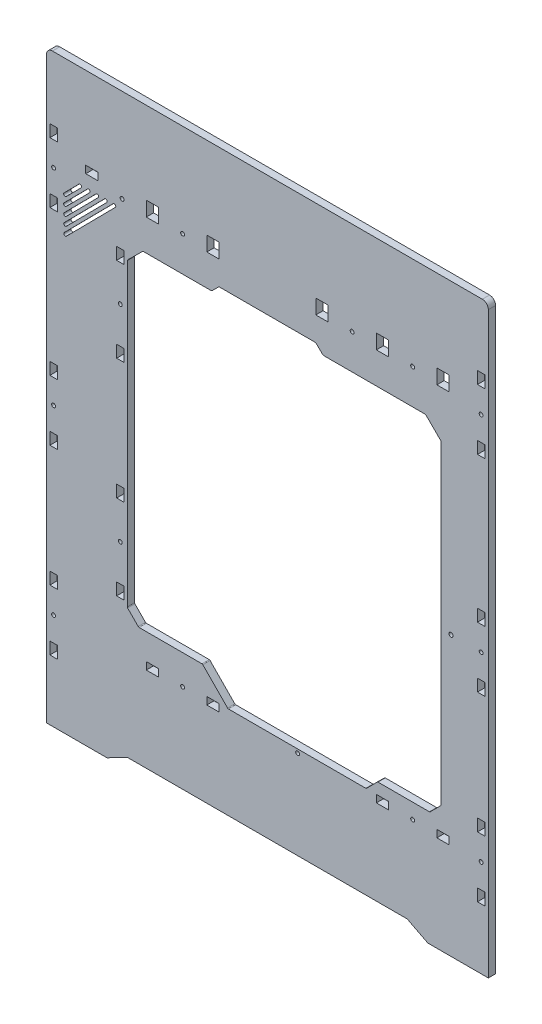
SolidWorks part; units mm, degrees
material "Клен"
ref_plane "Front" through (0, 0, 0) normal (0, 0, 1) x (1, 0, 0)
ref_plane "Top" through (0, 0, 0) normal (0, 1, 0) x (1, 0, 0)
ref_plane "Right" through (0, 0, 0) normal (1, 0, 0) x (0, 0, -1)
sketch "Эскиз1" plane through (0, 0, 0) normal (0, 0, 1) x (1, 0, 0)
  line L1 (768.3665, 485.0072) -> (768.3665, 477.0072)
  line L2 (745.3154, 525.0072) -> (1160.2565, 525.0072) construction
  line L3 (768.3665, 485.0072) -> (768.3665, 520.0072)
  line L4 (773.3665, 525.0072) -> (1128.3665, 525.0072)
  line L5 (1133.3665, 520.0072) -> (1133.3665, 485.0072)
  line L8 (1124.3665, 292.0072) -> (1130.4665, 292.0072)
  line L9 (1124.3665, 302.0072) -> (1124.3665, 292.0072)
  line L10 (1130.4665, 302.0072) -> (1124.3665, 302.0072)
  line L11 (1130.4665, 292.0072) -> (1130.4665, 302.0072)
  line L32 (1133.3665, 42.0072) -> (1133.3665, 477.0072)
  line L42 (768.3665, 477.0072) -> (768.3665, 42.0072)
  line L43 (768.3665, 42.0072) -> (818.3665, 42.0072)
  line L44 (818.3665, 42.0072) -> (835.3665, 50.7375)
  line L45 (835.3665, 50.7375) -> (1066.3665, 50.7375)
  line L46 (1066.3665, 50.7375) -> (1083.3665, 42.0072)
  line L47 (1083.3665, 42.0072) -> (1133.3665, 42.0072)
  line L48 (1124.3665, 242.0072) -> (1130.4665, 242.0072)
  line L49 (1124.3665, 252.0072) -> (1124.3665, 242.0072)
  line L50 (1130.4665, 252.0072) -> (1124.3665, 252.0072)
  line L51 (1130.4665, 242.0072) -> (1130.4665, 252.0072)
  line L56 (1124.3665, 142.0072) -> (1130.4665, 142.0072)
  line L57 (1124.3665, 152.0072) -> (1124.3665, 142.0072)
  line L58 (1130.4665, 152.0072) -> (1124.3665, 152.0072)
  line L59 (1130.4665, 142.0072) -> (1130.4665, 152.0072)
  line L64 (1124.3665, 92.0072) -> (1130.4665, 92.0072)
  line L65 (1124.3665, 102.0072) -> (1124.3665, 92.0072)
  line L66 (1130.4665, 102.0072) -> (1124.3665, 102.0072)
  line L67 (1130.4665, 92.0072) -> (1130.4665, 102.0072)
  line L72 (1100.8665, 127.1049) -> (1090.8665, 127.1049)
  line L73 (1100.8665, 121.0049) -> (1100.8665, 127.1049)
  line L74 (1090.8665, 121.0049) -> (1100.8665, 121.0049)
  line L75 (1090.8665, 127.1049) -> (1090.8665, 121.0049)
  line L80 (1050.8665, 127.1049) -> (1040.8665, 127.1049)
  line L81 (1050.8665, 121.0049) -> (1050.8665, 127.1049)
  line L82 (1040.8665, 121.0049) -> (1050.8665, 121.0049)
  line L83 (1040.8665, 127.1049) -> (1040.8665, 121.0049)
  line L96 (910.8665, 121.0049) -> (910.8665, 127.1049)
  line L97 (900.8665, 121.0049) -> (910.8665, 121.0049)
  line L98 (900.8665, 127.1049) -> (900.8665, 121.0049)
  line L99 (910.8665, 127.1049) -> (900.8665, 127.1049)
  line L104 (860.8665, 121.0049) -> (860.8665, 127.1049)
  line L105 (850.8665, 121.0049) -> (860.8665, 121.0049)
  line L106 (850.8665, 127.1049) -> (850.8665, 121.0049)
  line L107 (860.8665, 127.1049) -> (850.8665, 127.1049)
  line L112 (771.2665, 102.0072) -> (771.2665, 92.0072)
  line L113 (777.3665, 102.0072) -> (771.2665, 102.0072)
  line L114 (777.3665, 92.0072) -> (777.3665, 102.0072)
  line L115 (771.2665, 92.0072) -> (777.3665, 92.0072)
  line L120 (771.2665, 152.0072) -> (771.2665, 142.0072)
  line L121 (777.3665, 152.0072) -> (771.2665, 152.0072)
  line L122 (777.3665, 142.0072) -> (777.3665, 152.0072)
  line L123 (771.2665, 142.0072) -> (777.3665, 142.0072)
  line L128 (826.3665, 171.8072) -> (826.3665, 161.8072)
  line L129 (832.4665, 171.8072) -> (826.3665, 171.8072)
  line L130 (832.4665, 161.8072) -> (832.4665, 171.8072)
  line L131 (826.3665, 161.8072) -> (832.4665, 161.8072)
  line L136 (826.3665, 241.8072) -> (826.3665, 231.8072)
  line L137 (832.4665, 241.8072) -> (826.3665, 241.8072)
  line L138 (832.4665, 231.8072) -> (832.4665, 241.8072)
  line L139 (826.3665, 231.8072) -> (832.4665, 231.8072)
  line L144 (771.2665, 252.0072) -> (771.2665, 242.0072)
  line L145 (777.3665, 252.0072) -> (771.2665, 252.0072)
  line L146 (777.3665, 242.0072) -> (777.3665, 252.0072)
  line L147 (771.2665, 242.0072) -> (777.3665, 242.0072)
  line L152 (1124.3665, 412.0072) -> (1130.4665, 412.0072)
  line L153 (1124.3665, 422.0072) -> (1124.3665, 412.0072)
  line L154 (1130.4665, 422.0072) -> (1124.3665, 422.0072)
  line L155 (1130.4665, 412.0072) -> (1130.4665, 422.0072)
  line L160 (1124.3665, 462.0072) -> (1130.4665, 462.0072)
  line L161 (1124.3665, 472.0072) -> (1124.3665, 462.0072)
  line L162 (1130.4665, 472.0072) -> (1124.3665, 472.0072)
  line L163 (1130.4665, 462.0072) -> (1130.4665, 472.0072)
  line L168 (1090.8665, 457.1072) -> (1090.8665, 445.0072)
  line L169 (1100.8665, 457.1072) -> (1090.8665, 457.1072)
  line L170 (1100.8665, 445.0072) -> (1100.8665, 457.1072)
  line L171 (1090.8665, 445.0072) -> (1100.8665, 445.0072)
  line L176 (1040.8665, 457.1072) -> (1040.8665, 445.0072)
  line L177 (1050.8665, 457.1072) -> (1040.8665, 457.1072)
  line L178 (1050.8665, 445.0072) -> (1050.8665, 457.1072)
  line L179 (1040.8665, 445.0072) -> (1050.8665, 445.0072)
  line L184 (990.8665, 457.1072) -> (990.8665, 445.0072)
  line L185 (1000.8665, 457.1072) -> (990.8665, 457.1072)
  line L186 (1000.8665, 445.0072) -> (1000.8665, 457.1072)
  line L187 (990.8665, 445.0072) -> (1000.8665, 445.0072)
  line L192 (900.8665, 445.0072) -> (910.8665, 445.0072)
  line L193 (900.8665, 457.1072) -> (900.8665, 445.0072)
  line L194 (910.8665, 457.1072) -> (900.8665, 457.1072)
  line L195 (910.8665, 445.0072) -> (910.8665, 457.1072)
  line L200 (826.3665, 411.8072) -> (826.3665, 401.8072)
  line L201 (832.4665, 411.8072) -> (826.3665, 411.8072)
  line L202 (832.4665, 401.8072) -> (832.4665, 411.8072)
  line L203 (826.3665, 401.8072) -> (832.4665, 401.8072)
  line L224 (996.2808, 419.7551) -> (991.4523, 424.5835)
  line L225 (1081.1223, 419.1693) -> (997.695, 419.1693)
  line L226 (1094.1201, 406.6723) -> (1081.8269, 418.8789)
  line L227 (1094.4155, 146.42) -> (1094.4155, 405.9627)
  line L228 (1085.3572, 136.8536) -> (1094.1263, 145.7167)
  line L229 (1042.289, 136.5569) -> (1084.6463, 136.5569)
  line L230 (1032.8134, 127.4016) -> (1041.5781, 136.2603)
  line L231 (918.729, 127.1049) -> (1032.1025, 127.1049)
  line L232 (897.5745, 148.2016) -> (918.0158, 127.4039)
  line L233 (844.9385, 148.5006) -> (896.8613, 148.5006)
  line L234 (835.4584, 157.6604) -> (844.2276, 148.7973)
  line L235 (835.1693, 405.9627) -> (835.1693, 158.3637)
  line L236 (847.7579, 418.8789) -> (835.4647, 406.6723)
  line L237 (904.0381, 419.1693) -> (848.4625, 419.1693)
  line L238 (910.2808, 424.5835) -> (905.4523, 419.7551)
  line L239 (990.0381, 425.1693) -> (911.695, 425.1693)
  line L240 (850.8665, 445.0072) -> (860.8665, 445.0072)
  line L241 (850.8665, 457.1072) -> (850.8665, 445.0072)
  line L242 (860.8665, 457.1072) -> (850.8665, 457.1072)
  line L243 (860.8665, 445.0072) -> (860.8665, 457.1072)
  line L244 (784.8721, 398.2711) -> (825.3055, 439.1538)
  line L245 (823.528, 440.9118) -> (783.0946, 400.0291)
  line L248 (784.8331, 405.3421) -> (818.2346, 439.1147)
  line L249 (816.4571, 440.8727) -> (783.0556, 407.1001)
  line L252 (784.794, 412.4131) -> (811.1636, 439.0757)
  line L253 (809.3861, 440.8336) -> (783.0165, 414.171)
  line L256 (784.7549, 419.484) -> (804.0927, 439.0366)
  line L257 (802.3151, 440.7946) -> (782.9774, 421.242)
  line L260 (784.7159, 426.555) -> (797.0217, 438.9975)
  line L261 (795.2442, 440.7555) -> (782.9384, 428.313)
  line L263 (1133.3665, 485.0072) -> (1133.3665, 477.0072)
  line L268 (771.2665, 422.0072) -> (771.2665, 412.0072)
  line L269 (777.3665, 422.0072) -> (771.2665, 422.0072)
  line L270 (777.3665, 412.0072) -> (777.3665, 422.0072)
  line L271 (771.2665, 412.0072) -> (777.3665, 412.0072)
  line L276 (800.8665, 451.0072) -> (810.8665, 451.0072)
  line L277 (800.8665, 457.1072) -> (800.8665, 451.0072)
  line L278 (810.8665, 457.1072) -> (800.8665, 457.1072)
  line L279 (810.8665, 451.0072) -> (810.8665, 457.1072)
  line L284 (771.2665, 472.0072) -> (771.2665, 462.0072)
  line L285 (777.3665, 472.0072) -> (771.2665, 472.0072)
  line L286 (777.3665, 462.0072) -> (777.3665, 472.0072)
  line L287 (771.2665, 462.0072) -> (777.3665, 462.0072)
  line L292 (826.3665, 341.8072) -> (826.3665, 331.8072)
  line L293 (832.4665, 341.8072) -> (826.3665, 341.8072)
  line L294 (832.4665, 331.8072) -> (832.4665, 341.8072)
  line L295 (826.3665, 331.8072) -> (832.4665, 331.8072)
  line L300 (771.2665, 302.0072) -> (771.2665, 292.0072)
  line L301 (777.3665, 302.0072) -> (771.2665, 302.0072)
  line L302 (777.3665, 292.0072) -> (777.3665, 302.0072)
  line L303 (771.2665, 292.0072) -> (777.3665, 292.0072)
  arc A1 (1128.3665, 525.0072) -> (1133.3665, 520.0072) centre (1128.3665, 520.0072) cw
  circle A2 centre (1127.4165, 272.0072) radius 1.6
  arc A3 (768.3665, 520.0072) -> (773.3665, 525.0072) centre (773.3665, 520.0072) cw
  circle A4 centre (1102.521, 272.0072) radius 1.7
  circle A6 centre (1127.4165, 122.0072) radius 1.6
  circle A24 centre (1070.8665, 124.0549) radius 1.6
  circle A26 centre (975.8665, 124.0549) radius 1.6
  circle A28 centre (880.8665, 124.0549) radius 1.6
  circle A38 centre (774.3165, 122.0072) radius 1.6
  circle A40 centre (829.4165, 202.0072) radius 1.6
  circle A42 centre (774.3165, 272.0072) radius 1.6
  circle A44 centre (1127.4165, 442.0072) radius 1.6
  circle A46 centre (1070.8665, 448.0572) radius 1.6
  circle A48 centre (1020.8665, 448.0572) radius 1.6
  circle A50 centre (880.8665, 448.0572) radius 1.6
  circle A52 centre (830.8665, 448.0572) radius 1.6
  arc A56 (825.3055, 439.1538) -> (823.528, 440.9118) centre (824.4168, 440.0328) ccw
  arc A57 (783.0946, 400.0291) -> (784.8721, 398.2711) centre (783.9834, 399.1501) ccw
  arc A60 (818.2346, 439.1147) -> (816.4571, 440.8727) centre (817.3458, 439.9937) ccw
  arc A61 (783.0556, 407.1001) -> (784.8331, 405.3421) centre (783.9443, 406.2211) ccw
  arc A64 (811.1636, 439.0757) -> (809.3861, 440.8336) centre (810.2749, 439.9546) ccw
  arc A65 (783.0165, 414.171) -> (784.794, 412.4131) centre (783.9053, 413.292) ccw
  arc A82 (991.4523, 424.5835) -> (990.0381, 425.1693) centre (990.0381, 423.1693) ccw
  arc A83 (996.2808, 419.7551) -> (997.695, 419.1693) centre (997.695, 421.1693) ccw
  arc A84 (1081.8269, 418.8789) -> (1081.1223, 419.1693) centre (1081.1223, 418.1693) ccw
  arc A85 (1094.4155, 405.9627) -> (1094.1201, 406.6723) centre (1093.4155, 405.9627) ccw
  arc A86 (1094.1263, 145.7167) -> (1094.4155, 146.42) centre (1093.4155, 146.42) ccw
  arc A87 (1084.6463, 136.5569) -> (1085.3572, 136.8536) centre (1084.6463, 137.5569) ccw
  arc A88 (1042.289, 136.5569) -> (1041.5781, 136.2603) centre (1042.289, 135.5569) ccw
  arc A89 (1032.1025, 127.1049) -> (1032.8134, 127.4016) centre (1032.1025, 128.1049) ccw
  arc A90 (918.0158, 127.4039) -> (918.729, 127.1049) centre (918.729, 128.1049) ccw
  arc A91 (897.5745, 148.2016) -> (896.8613, 148.5006) centre (896.8613, 147.5006) ccw
  arc A92 (844.2276, 148.7973) -> (844.9385, 148.5006) centre (844.9385, 149.5006) ccw
  arc A93 (835.1693, 158.3637) -> (835.4584, 157.6604) centre (836.1693, 158.3637) ccw
  arc A94 (835.4647, 406.6723) -> (835.1693, 405.9627) centre (836.1693, 405.9627) ccw
  arc A95 (848.4625, 419.1693) -> (847.7579, 418.8789) centre (848.4625, 418.1693) ccw
  arc A96 (904.0381, 419.1693) -> (905.4523, 419.7551) centre (904.0381, 421.1693) ccw
  arc A97 (911.695, 425.1693) -> (910.2808, 424.5835) centre (911.695, 423.1693) ccw
  arc A100 (804.0927, 439.0366) -> (802.3151, 440.7946) centre (803.2039, 439.9156) ccw
  arc A101 (782.9774, 421.242) -> (784.7549, 419.484) centre (783.8662, 420.363) ccw
  arc A104 (797.0217, 438.9975) -> (795.2442, 440.7555) centre (796.1329, 439.8765) ccw
  arc A105 (782.9384, 428.313) -> (784.7159, 426.555) centre (783.8271, 427.434) ccw
  circle A106 centre (774.3165, 442.0072) radius 1.6
  circle A108 centre (829.4165, 372.0072) radius 1.6
  point P10 (1133.3665, 525.0072)
  point P14 (768.3665, 525.0072)
  point P15 (829.4165, 401.8072)
  dimension "D1" = 5
  dimension "D2" = 113.2
  dimension "D3" = 60
  dimension "D4" = 90
  dimension "D5" = 60
extrude "Бобышка-Вытянуть1" add sketch "Эскиз1" along normal blind 6 contours L1 L42 L43 L44 L45 L46 L47 L32 L263 L11 L8 L9 L10 L51 L48 L49 L50 L59 L56 L57 L58 L67 L64 L65 L66 L75 L72 L73 L74 L83 L80 L81 L82 L99 L96 L97 L98 region at (774.4206, 502.5072, 0)
